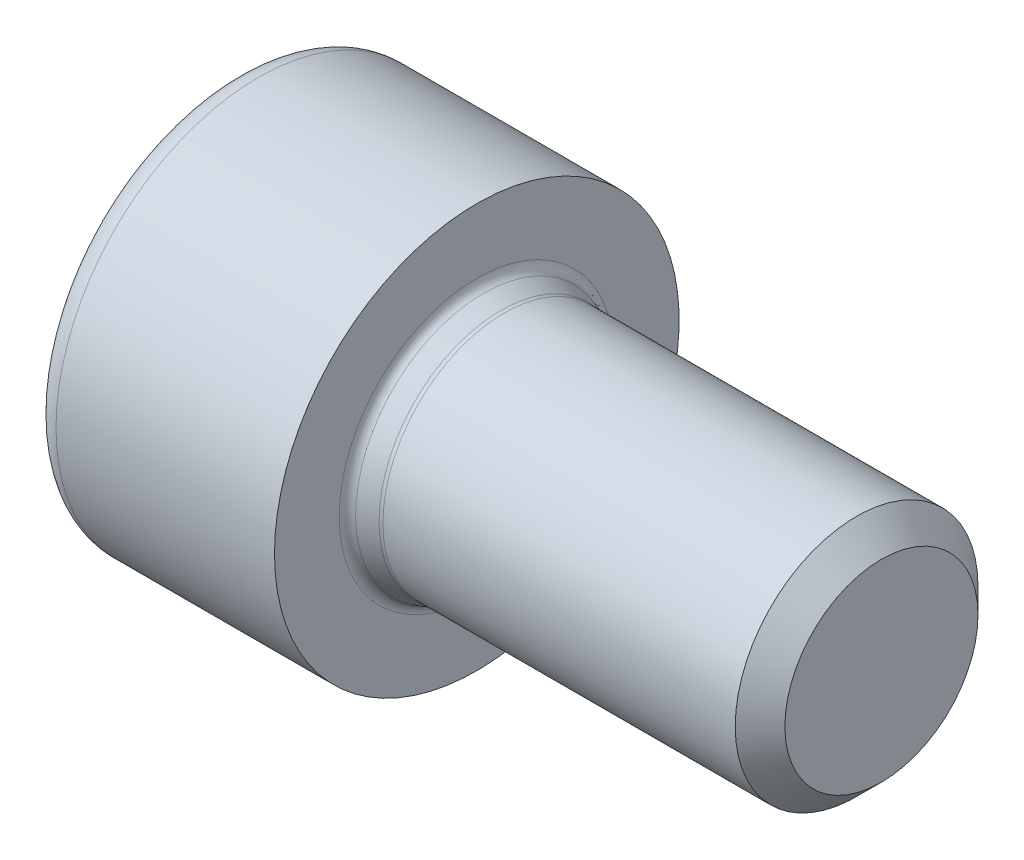
SolidWorks part; units mm, degrees
note: '?' marks a value the reader was unsure of.
ref_plane "前视基准面" through (0, 0, 0) normal (0, 0, 1) x (1, 0, 0)
ref_plane "上视基准面" through (0, 0, 0) normal (0, 1, 0) x (1, 0, 0)
ref_plane "右视基准面" through (0, 0, 0) normal (1, 0, 0) x (0, 0, -1)
sketch "草图1" plane through (0, 0, 0) normal (0, 0, 1) x (1, 0, 0)
  line L0 (-0.8566, 0) -> (-2.3, 2.5)
  line L1 (-2.3, 2.5) -> (-6, 2.5)
  line L2 (-6, 2.5) -> (-6, 4.4)
  line L3 (-5.4, 5) -> (0, 5)
  line L4 (0, 5) -> (0, 3.4)
  line L5 (0.1677, 3.1639) -> (0.5977, 3.0139)
  line L6 (0.68, 3) -> (9.3865, 3)
  line L7 (9.3865, 3) -> (10, 2.3865)
  line L8 (10, 2.3865) -> (10, 0)
  line L9 (10, 0) -> (-0.8566, 0)
  line L10 (10, 0) -> (-0.8566, 0) construction
  arc A0 (-6, 4.4) -> (-5.4, 5) centre (-5.4, 4.4) cw
  arc A1 (0, 3.4) -> (0.1677, 3.1639) centre (0.25, 3.4) ccw
  arc A2 (0.5977, 3.0139) -> (0.68, 3) centre (0.68, 3.25) ccw
revolve "旋转1" add sketch "草图1" angle 360 about L10
cosmetic thread "装饰螺纹线1" parameters "D1"=3, "D2"=4.773
ref_plane "基准面4" through (-2.3, 0, 0) normal (1, 0, 0) x (0, 0, -1)
sketch "草图2" plane through (-2.3, 0, 0) normal (1, 0, 0) x (0, 0, -1)
  line L0 (-2.5, 1.4434) -> (-2.5, -1.4434)
  line L1 (-2.5, -1.4434) -> (0, -2.8868)
  line L2 (0, -2.8868) -> (2.5, -1.4434)
  line L3 (2.5, -1.4434) -> (2.5, 1.4434)
  line L4 (2.5, 1.4434) -> (0, 2.8868)
  line L5 (0, 2.8868) -> (-2.5, 1.4434)
extrude "切除-拉伸1" cut sketch "草图2" against normal blind 6
ref_plane "基准面5" through (0, 0, 0) normal (1, 0, 0) x (0, 0, -1)
ref_plane "基准面6" through (10, 0, 0) normal (1, 0, 0) x (0, 0, -1)
ref_plane "基准面7" through (-6, 0, 0) normal (1, 0, 0) x (0, 0, -1)
ref_plane "IP1 XY" through (0, 0, 0) normal (1, 0, 0) x (0, 0, -1)
ref_plane "IP1 XZ" through (0, 0, 0) normal (0, -1, 0) x (-1, 0, 0)
ref_plane "IP1 YZ" through (0, 0, 0) normal (0, 0, -1) x (-1, 0, 0)
ref_axis "IP1 X" through (0, 0, 80.9) along (0, 0, -1)?
ref_axis "IP1 Y" through (0, -50, 0) along (0, 1, 0)?
ref_axis "IP1 Z" through (80.9, 0, 0) along (-1, 0, 0)?
sketch3d "IP1"
  point P0 (0, 0, 0)
ref_plane "IP3 XY" through (10, 0, 0) normal (1, 0, 0) x (0, 0, -1)
ref_plane "IP3 XZ" through (0, 0, 0) normal (0, -1, 0) x (-1, 0, 0)
ref_plane "IP3 YZ" through (0, 0, 0) normal (0, 0, -1) x (-1, 0, 0)
ref_axis "IP3 X" through (10, 0, 80.9) along (0, 0, -1)?
ref_axis "IP3 Y" through (10, -50, 0) along (0, 1, 0)?
ref_axis "IP3 Z" through (80.9, 0, 0) along (-1, 0, 0)?
sketch3d "IP3"
  point P0 (10, 0, 0)
ref_plane "IP2 XY" through (-6, 0, 0) normal (1, 0, 0) x (0, 0, -1)
ref_plane "IP2 XZ" through (0, 0, 0) normal (0, -1, 0) x (-1, 0, 0)
ref_plane "IP2 YZ" through (0, 0, 0) normal (0, 0, -1) x (-1, 0, 0)
ref_axis "IP2 X" through (-6, 0, 80.9) along (0, 0, -1)?
ref_axis "IP2 Y" through (-6, -50, 0) along (0, 1, 0)?
ref_axis "IP2 Z" through (80.9, 0, 0) along (-1, 0, 0)?
sketch3d "IP2"
  point P0 (-6, 0, 0)
ref_plane "IP4 XY" through (0, 0, 0) normal (1, 0, 0) x (0, 0, -1)
ref_plane "IP4 XZ" through (0, 0, 0) normal (0, -1, 0) x (-1, 0, 0)
ref_plane "IP4 YZ" through (0, 0, 0) normal (0, 0, -1) x (-1, 0, 0)
ref_axis "IP4 X" through (0, 0, 80.9) along (0, 0, -1)?
ref_axis "IP4 Y" through (0, -50, 0) along (0, 1, 0)?
ref_axis "IP4 Z" through (80.9, 0, 0) along (-1, 0, 0)?
sketch3d "IP4"
  point P0 (0, 0, 0)
sketch "草图3" plane through (0, 0, 0) normal (1, 0, 0) x (0, 0, -1)
  circle A0 centre (0, 0) radius 3.75
extrude "凸台-拉伸1" add sketch "草图3" against normal blind 3 separate body
other "删除面1" face at (-3, 0, -3.75)
